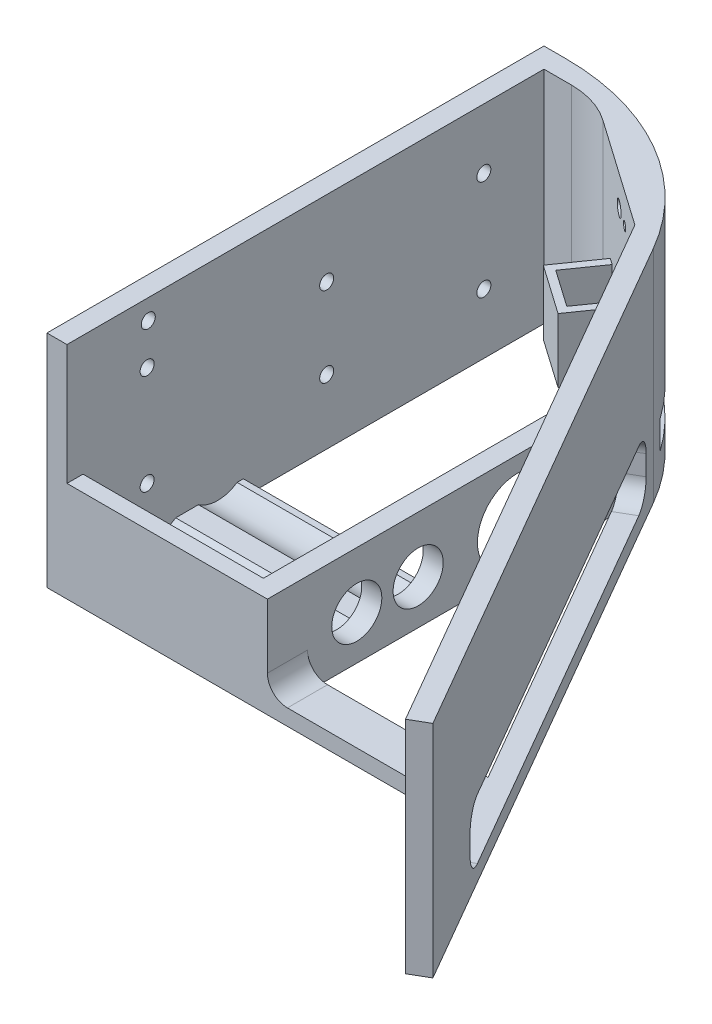
SolidWorks part; units mm, degrees
ref_plane "Front" through (0, 0, 0) normal (0, 0, 1) x (1, 0, 0)
ref_plane "Top" through (0, 0, 0) normal (0, 1, 0) x (1, 0, 0)
ref_plane "Right" through (0, 0, 0) normal (1, 0, 0) x (0, 0, -1)
sketch "Sketch3" plane through (0, 0, 0) normal (0, 1, 0) x (1, 0, 0)
  line L0 (128.1699, -162.7147) -> (55, -35.9808)
  line L1 (0, 0) -> (40, 0)
  line L2 (0, 0) -> (0, -124)
  line L3 (0, -124) -> (5, -124)
  line L4 (5, -5) -> (5, -124)
  line L5 (40, 0) -> (132.5, -160.2147)
  line L6 (132.5, -160.2147) -> (128.1699, -162.7147)
  line L7 (5, -5) -> (18.123, -5)
  line L10 (50, -27.3205) -> (50, -124)
  line L11 (50, -124) -> (55, -124)
  line L12 (55, -35.9808) -> (55, -124)
  line L13 (18.123, -5) -> (50, -27.3205)
  point P7 (44.3301, -17.5)
  point P11 (0, 0)
  point P12 (45, -18.5066)
  point P14 (1.3397, -5)
  point P15 (22.4588, -5)
  dimension "D1" = 5
  dimension "D2" = 5
  dimension "D3" = 5
  dimension "D4" = 120
  dimension "D5" = 124
  dimension "D6" = 185
  dimension "D7" = 40
  dimension "D8" = 5
  dimension "D9" = 45
  dimension "D10" = 145
extrude "Boss-Extrude3" add sketch "Sketch3" along normal blind 55 contours L2 L3 L4 L7 L13 L10 L11 L12 L0 L6 L5 L1
fillet "Fillet1" radius 60 1 edges at (40, 27.5, 0)
sketch "Sketch4" plane through (3.6131, 0, -5.16) normal (-0.5736, 0, 0.8192) x (0.8192, 0, 0.5736)
  line L1 (31.628, 30.3662) -> (46.628, 30.3662)
  line L2 (31.628, 30.3662) -> (31.628, 14.3662)
  line L3 (31.628, 14.3662) -> (46.628, 14.3662)
  line L4 (46.628, 30.3662) -> (46.628, 14.3662)
  line L5 (56.628, 55) -> (56.628, 0) construction
  dimension "D1" = 15
  dimension "D2" = 16
  dimension "D3" = 10
extrude "Boss-Extrude4" add sketch "Sketch4" along normal blind 12
sketch "Sketch5" plane through (3.6131, 0, -5.16) normal (-0.5736, 0, 0.8192) x (0.8192, 0, 0.5736)
  line L1 (19.128, 14.3662) -> (59.128, 14.3662)
  line L2 (19.128, 14.3662) -> (19.128, 7.3662)
  line L3 (19.128, 7.3662) -> (59.128, 7.3662)
  line L4 (59.128, 14.3662) -> (59.128, 7.3662)
  line L5 (39.128, 14.3662) -> (39.128, -8.9782) construction
  line L6 (31.628, 14.3662) -> (46.628, 14.3662) construction
  dimension "D1" = 40
  dimension "D2" = 7
extrude "Cut-Extrude1" cut sketch "Sketch5" against normal blind 14 and the other way blind 20
sketch "Sketch6" plane through (0, 30.3662, 0) normal (0, 1, 0) x (1, 0, 0)
  line L0 (31.0776, -14.0709) -> (25.2845, -22.3443)
  line L1 (25.2845, -22.3443) -> (34.459, -28.7684)
  line L2 (34.459, -28.7684) -> (40.2521, -20.4949)
  line L3 (40.2521, -20.4949) -> (31.0776, -14.0709)
  line L4 (34.9256, -31.4146) -> (41.8085, -21.5847) construction
  line L5 (22.6383, -22.8109) -> (29.5212, -12.9811) construction
  line L6 (34.9256, -31.4146) -> (22.6383, -22.8109) construction
  line L7 (41.8085, -21.5847) -> (29.5212, -12.9811) construction
  dimension "D1" = 1.9
  dimension "D2" = 1.9
  dimension "D3" = 1.9
extrude "Cut-Extrude2" cut sketch "Sketch6" against normal offset from surface (14 mm away) 2 up to face at (36.2555, 14.3662, 19.8332)
sketch "Sketch7" plane through (0, 16.3662, 0) normal (0, 1, 0) x (1, 0, 0)
  line L0 (31.0776, -14.0709) -> (34.459, -28.7684) construction
  line L1 (34.459, -28.7684) -> (25.2845, -22.3443) construction
  circle A0 centre (32.7683, -21.4196) radius 2
  point P7 (31.7059, -16.7584)
  point P8 (34.4835, -28.9077)
  dimension "D1" = 4
extrude "Cut-Extrude3" cut sketch "Sketch7" against normal blind 2
sketch "Sketch8" plane through (0, 55, 0) normal (0, 1, 0) x (1, 0, 0)
  line L0 (55, -35.9808) -> (50, -27.3205)
  line L1 (50, -27.3205) -> (50, -124)
  line L2 (50, -124) -> (55, -124)
  line L3 (55, -124) -> (55, -35.9808)
extrude "Cut-Extrude4" cut sketch "Sketch8" against normal blind 30
sketch "Sketch9" plane through (50, 0, 0) normal (-1, 0, 0) x (0, 0, 1)
  line L0 (27.3205, 0) -> (124, 0) construction
  circle A0 centre (61.5987, 11) radius 10
  circle A1 centre (86.3851, 11) radius 6.25
  circle A2 centre (101.7, 11) radius 6.25
  point P6 (0, 0)
  point P7 (0, 0)
  dimension "D1" = 12.5
  dimension "D2" = 12.5
  dimension "D3" = 20
  dimension "D4" = 11
extrude "Cut-Extrude5" cut sketch "Sketch9" against normal up to surface (5 mm away) up to face at (55, 12.5, 79.9904)
sketch "Sketch10" plane through (30, 0, -17.3205) normal (0.866, 0, -0.5) x (-0.5, 0, -0.866)
  line L0 (-54.641, 0) -> (-205, 0) construction
  line L1 (-179.641, 4) -> (-59.641, 4)
  line L2 (-179.641, 4) -> (-179.641, 19)
  line L3 (-179.641, 19) -> (-59.641, 19)
  line L4 (-59.641, 4) -> (-59.641, 19)
  line L5 (-54.641, 0) -> (-54.641, 55) construction
  dimension "D1" = 15
  dimension "D2" = 4
  dimension "D3" = 120
  dimension "D4" = 5
extrude "Cut-Extrude6" cut sketch "Sketch10" against normal up to surface (5 mm away) up to face at (77.7233, 26.6667, 75.3387)
sketch "Sketch11" plane through (50, 0, 0) normal (-1, 0, 0) x (0, 0, 1)
  line L0 (27.3205, 0) -> (124, 0) construction
  line L1 (124, 25) -> (120, 25)
  line L2 (124, 25) -> (124, 0)
  line L3 (124, 0) -> (120, 0)
  line L4 (120, 25) -> (120, 0)
  dimension "D1" = 4
extrude "Boss-Extrude5" add sketch "Sketch11" along normal up to surface (45 mm away) up to face at (5, 27.5, 64.5)
fillet "Fillet3" radius 20 1 edges at (18.123, 27.5, 5)
sketch "Sketch12" plane through (55, 0, 0) normal (1, 0, 0) x (0, 0, -1)
  line L1 (-124, 0) -> (-114, 0)
  line L2 (-124, 0) -> (-124, 4)
  line L3 (-124, 4) -> (-114, 4)
  line L4 (-114, 0) -> (-114, 4)
  dimension "D1" = 10
  dimension "D2" = 4
extrude "Boss-Extrude6" add sketch "Sketch12" along normal up to surface (50.8179 mm away) up to face at (85.4904, 11.5, 88.7917)
sketch "Sketch13" plane through (50, 0, 0) normal (-1, 0, 0) x (0, 0, 1)
  line L1 (80, 0) -> (120, 0)
  line L2 (80, 0) -> (80, 4)
  line L3 (80, 4) -> (120, 4)
  line L4 (120, 0) -> (120, 4)
  line L5 (120, 25) -> (120, 0) construction
  point P8 (0, 0)
  dimension "D1" = 4
  dimension "D2" = 40
extrude "Boss-Extrude7" add sketch "Sketch13" along normal up to surface (45 mm away) up to face at (5, 26.6667, 83)
fillet "Fillet4" radius 5 4 edges at (57.6554, 4, 35.5801) (117.6554, 4, 139.5032) (117.6554, 19, 139.5032) (57.6554, 19, 35.5801)
fillet "Fillet5" radius 5 1 edges at (55, 4, 119)
sketch "Sketch14" plane through (50, 0, 0) normal (-1, 0, 0) x (0, 0, 1)
  arc A0 (94.0426, 14.6896) -> (94.0426, 7.3104) centre (86.3851, 11) ccw
  arc A1 (94.0426, 7.3104) -> (94.0426, 14.6896) centre (101.7, 11) ccw
  circle A2 centre (101.7, 11) radius 6.25 construction
  circle A3 centre (86.3851, 11) radius 6.25 construction
  point P4 (0, 0)
  dimension "D1" = 17
  dimension "D2" = 17
extrude "Cut-Extrude7" cut sketch "Sketch14" along normal up to surface (45 mm away) up to face at (5, 21, 82.25)
sketch "Sketch15" plane through (0, 0, 0) normal (-1, 0, 0) x (0, 0, 1)
  line L0 (0, 55) -> (124, 55) construction
  line L1 (0, 55) -> (0, 0) construction
  line L2 (0, 0) -> (124, 0) construction
  line L3 (124, 55) -> (124, 0) construction
  circle A0 centre (104, 40) radius 1.75
  circle A1 centre (104, 15) radius 1.75
  circle A2 centre (20, 15) radius 1.75
  circle A3 centre (20, 40) radius 1.75
  point P8 (0, 0)
  point P9 (0, 0)
  point P10 (0, 0)
  point P11 (0, 0)
  dimension "D1" = 3.5
  dimension "D2" = 15
  dimension "D3" = 20
  dimension "D4" = 15
  dimension "D5" = 20
sketch "Sketch16" plane through (0, 0, 0) normal (-1, 0, 0) x (0, 0, 1)
  circle A0 centre (59.2085, 36.1358) radius 1.75
  circle A1 centre (59.2085, 16.1358) radius 1.75
  circle A2 centre (103.7183, 50.0137) radius 1.75
  dimension "D1" = 3.5
  dimension "D2" = 3.5
  dimension "D3" = 3.5
extrude "Cut-Extrude8" cut sketch "Sketch16" against normal blind 5
extrude "Cut-Extrude9" cut sketch "Sketch15" against normal blind 5
sketch "Sketch17" plane through (30, 0, -17.3205) normal (0.866, 0, -0.5) x (-0.5, 0, -0.866)
  line L0 (-49.2023, 7.3662) -> (-49.2023, 14.3662) construction
  line L1 (-2.6795, 55) -> (-54.641, 55) construction
  circle A0 centre (-34.2023, 47.5) radius 1.75
  circle A1 centre (-39.2023, 47.5) radius 1
  dimension "D1" = 2
  dimension "D2" = 3.5
  dimension "D3" = 5
  dimension "D4" = 10
  dimension "D5" = 7.5
extrude "Cut-Extrude10" cut sketch "Sketch17" against normal up to next
